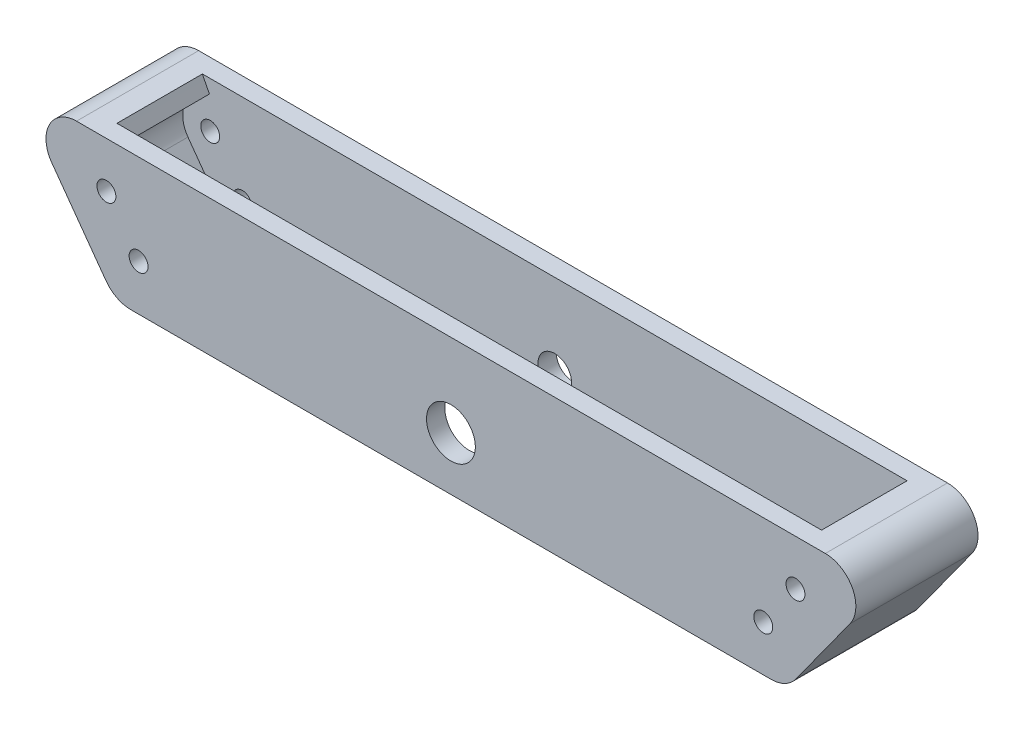
SolidWorks part; units mm, degrees
ref_plane "Front Plane" through (0, 0, 0) normal (0, 0, 1) x (1, 0, 0)
ref_plane "Top Plane" through (0, 0, 0) normal (0, 1, 0) x (1, 0, 0)
ref_plane "Right Plane" through (0, 0, 0) normal (1, 0, 0) x (0, 0, -1)
sketch "Sketch1" plane through (0, 0, 0) normal (0, 0, 1) x (1, 0, 0)
  line L0 (0, 0) -> (0, -62.5) construction
  line L1 (-71.0874, -27.7045) -> (0, -27.7045) construction
  line L2 (0, -50) -> (-54.9811, -50) construction
  line L3 (-54.9811, -50) -> (-71.0874, -27.7045) construction
  line L4 (-56.4171, -35.2045) -> (-51.1468, -42.5) construction
  line L5 (-71.0874, -27.7045) -> (-54.9811, -50)
  line L6 (-54.9811, -50) -> (-39.95, -50)
  line L7 (-71.0874, -27.7045) -> (-57.6928, -27.7045)
  line L8 (54.9811, -50) -> (39.95, -50)
  line L9 (71.0874, -27.7045) -> (54.9811, -50)
  line L10 (71.0874, -27.7045) -> (57.6928, -27.7045)
  line L11 (-58.7994, -31.3868) -> (-56.5441, -29.9795)
  line L12 (48.7646, -46.3177) -> (45.9424, -44.5566)
  line L13 (-56.4171, -35.2045) -> (0, 0) construction
  line L14 (-60.0649, -37.8397) -> (-54.7946, -45.1351)
  line L15 (-48.7646, -46.3177) -> (-45.9424, -44.5566)
  line L16 (60.0649, -37.8397) -> (54.7946, -45.1351)
  line L17 (58.7994, -31.3868) -> (56.5441, -29.9795)
  circle A0 centre (0, 0) radius 62.5 construction
  circle A2 centre (0, -41.25) radius 4
  circle A3 centre (-56.4171, -35.2045) radius 4 construction
  circle A4 centre (-51.1468, -42.5) radius 4 construction
  circle A5 centre (-56.4171, -35.2045) radius 1.55
  circle A6 centre (-51.1468, -42.5) radius 1.55
  circle A7 centre (0, -41.25) radius 15
  circle A8 centre (0, 0) radius 55.5 construction
  circle A9 centre (0, 0) radius 56.25 construction
  circle A10 centre (0, 0) radius 64 construction
  arc A11 (-57.6928, -27.7045) -> (-39.95, -50) centre (0, 0) ccw
  arc A12 (57.6928, -27.7045) -> (39.95, -50) centre (0, 0) cw
  circle A13 centre (51.1468, -42.5) radius 1.55
  circle A14 centre (56.4171, -35.2045) radius 1.55
  circle A15 centre (-56.4171, -35.2045) radius 4.5 construction
  arc A16 (-58.7994, -31.3868) -> (-60.0649, -37.8397) centre (-56.4171, -35.2045) ccw
  circle A17 centre (-51.1468, -42.5) radius 4.5 construction
  arc A18 (-48.7646, -46.3177) -> (-54.7946, -45.1351) centre (-51.1468, -42.5) cw
  arc A19 (48.7646, -46.3177) -> (54.7946, -45.1351) centre (51.1468, -42.5) ccw
  arc A20 (58.7994, -31.3868) -> (60.0649, -37.8397) centre (56.4171, -35.2045) cw
  point P26 (0, 0)
  dimension "D1" = 125
  dimension "D3" = 8
  dimension "D4" = 8
  dimension "D9" = 3.1
  dimension "D11" = 30
  dimension "D12" = 112.5
  dimension "D13" = 128
  dimension "D14" = 9
  dimension "D15" = 9
  dimension "D5" = 9
  dimension "D6" = 20
  dimension "D7" = 7.5
  dimension "D8" = 7.5
  dimension "D10" = 7.5
  dimension "D2" = 7
extrude "Boss-Extrude1" add sketch "Sketch1" along normal mid plane 14 contours A11 L7 L5 L6 A6 A5 | L10 A12 L8 L9 A13 A14 region at (-64.3901, -28.0875, 0) region at (47.4655, -49.617, 0)
sketch "Sketch2" plane through (0, 0, 7) normal (0, 0, 1) x (1, 0, 0)
  line L0 (-54.9811, -50) -> (54.9811, -50)
  line L1 (54.9811, -50) -> (71.0874, -27.7045)
  line L2 (71.0874, -27.7045) -> (-71.0874, -27.7045)
  line L3 (-71.0874, -27.7045) -> (-54.9811, -50)
  circle A0 centre (0, -41.25) radius 4 construction
  circle A1 centre (0, -41.25) radius 4
  circle A10 centre (-51.1468, -42.5) radius 1.55 construction
  circle A11 centre (-56.4171, -35.2045) radius 1.55 construction
  circle A12 centre (-51.1468, -42.5) radius 1.55
  circle A13 centre (-56.4171, -35.2045) radius 1.55
  circle A14 centre (56.4171, -35.2045) radius 1.55 construction
  circle A15 centre (51.1468, -42.5) radius 1.55 construction
  circle A16 centre (56.4171, -35.2045) radius 1.55
  circle A17 centre (51.1468, -42.5) radius 1.55
extrude "Boss-Extrude2" add sketch "Sketch2" along normal blind 3
mirror "Mirror2" about plane through (0, 0, 0) normal (0, 0, 1) of "Boss-Extrude2"
fillet "Fillet1" radius 5 4 edges at (-54.9811, -50, 0) (54.9811, -50, 0) (71.0874, -27.7045, 0) (-71.0874, -27.7045, 0)
fillet "Fillet2" radius 1 2 edges at (39.95, -50, 0) (-39.95, -50, 0)
sketch "Sketch3" plane through (0, 0, -10) normal (0, 0, -1) x (-1, 0, 0)
  circle A0 centre (0, -41.25) radius 2.75
  circle A1 centre (0, -41.25) radius 6.0148
  dimension "D1" = 5.5
extrude "Boss-Extrude3" add sketch "Sketch3" against normal up to surface (3 mm away) up to face at (0, -40.2617, -7)
equation "\"D12@Sketch1\"=75*1.5"
equation "\"D11@Sketch1\"=20*1.5"
